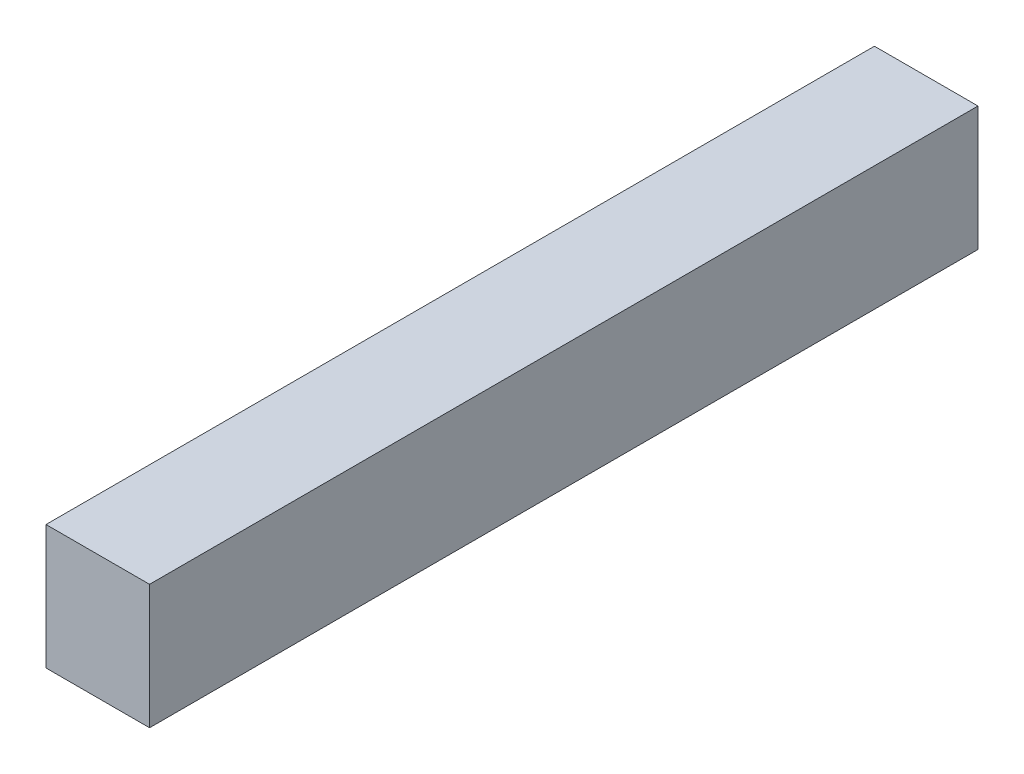
SolidWorks part; units mm, degrees
ref_plane "Front Plane" through (0, 0, 0) normal (0, 0, 1) x (1, 0, 0)
ref_plane "Top Plane" through (0, 0, 0) normal (0, 1, 0) x (1, 0, 0)
ref_plane "Right Plane" through (0, 0, 0) normal (1, 0, 0) x (0, 0, -1)
sketch "Sketch1" plane through (0, 0, 0) normal (0, 0, 1) x (1, 0, 0)
  line L1 (-12.5, -15) -> (12.5, -15)
  line L2 (-12.5, -15) -> (-12.5, 15)
  line L3 (-12.5, 15) -> (12.5, 15)
  line L4 (12.5, -15) -> (12.5, 15)
  line L5 (-12.5, -15) -> (12.5, 15) construction
  line L6 (-12.5, 15) -> (12.5, -15) construction
  point P0 (0, 0)
  dimension "D1" = 25
  dimension "D2" = 30
extrude "Boss-Extrude1" add sketch "Sketch1" along normal blind 100 and the other way blind 100
sketch "Sketch3" plane through (12.5, 0, 0) normal (1, 0, 0) x (0, 0, -1)
  line L0 (0, 15) -> (0, -15)
  line L1 (100, 15) -> (-100, 15) construction
  line L2 (100, -15) -> (-100, -15) construction
